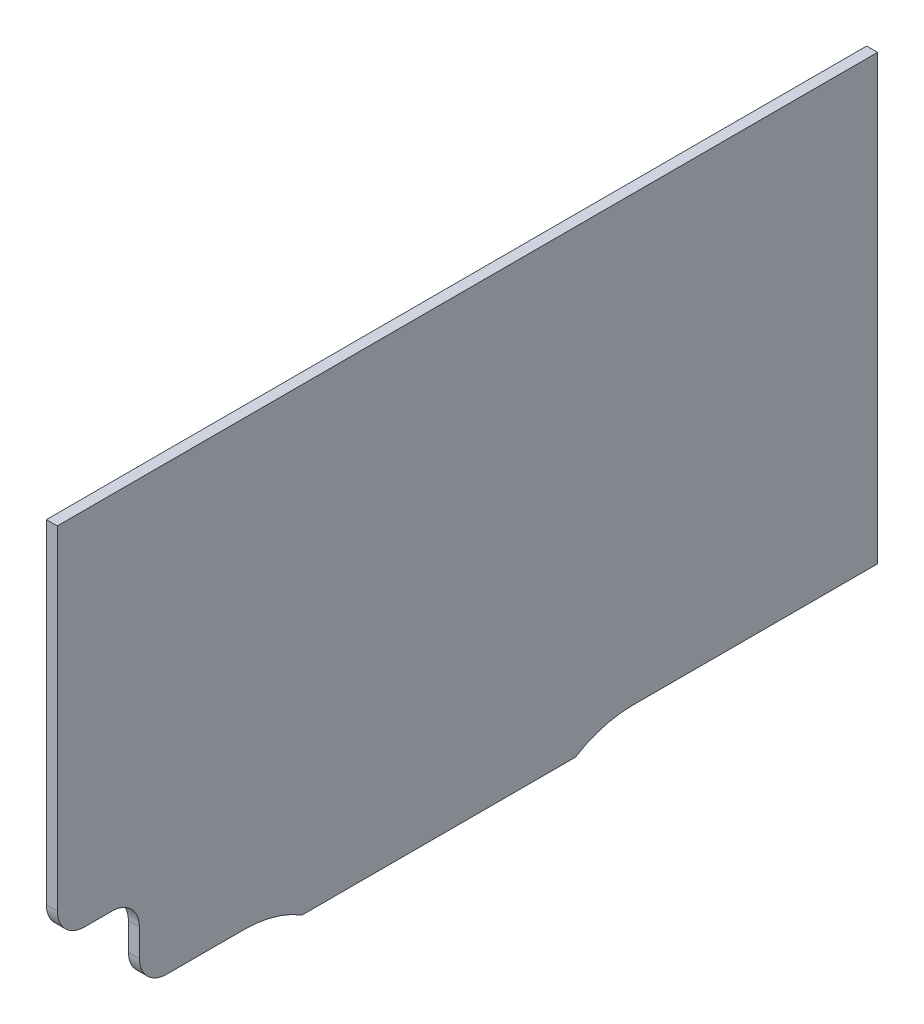
SolidWorks part; units mm, degrees
ref_plane "Alzado" through (0, 0, 0) normal (0, 0, 1) x (1, 0, 0)
ref_plane "Planta" through (0, 0, 0) normal (0, 1, 0) x (1, 0, 0)
ref_plane "Vista lateral" through (0, 0, 0) normal (1, 0, 0) x (0, 0, -1)
sketch "Croquis1" plane through (0, 0, 0) normal (0, 1, 0) x (1, 0, 0)
  line L0 (10, 50) -> (10, 0) construction
  line L1 (0, 0) -> (25, 0)
  line L2 (0, 0) -> (0, 50)
  line L3 (0, 50) -> (25, 50)
  line L4 (25, 0) -> (25, 50)
  circle A0 centre (10, 37.5) radius 1.65
  circle A1 centre (10, 12.5) radius 1.65
  dimension "D3" = 3.3
  dimension "D1" = 50
  dimension "D2" = 25
  dimension "D4" = 25
  dimension "D5" = 12.5
  dimension "D6" = 15
extrude "Saliente-Extruir1" add sketch "Croquis1" along normal blind 3
sketch "Croquis2" plane through (0, 3, 0) normal (0, 1, 0) x (1, 0, 0)
  line L0 (25, 25) -> (18, 25) construction
  line L1 (16, 105.25) -> (18, 105.25)
  line L2 (16, 105.25) -> (16, -44.75)
  line L3 (16, -44.75) -> (18, -44.75)
  line L4 (18, 105.25) -> (18, -44.75)
  line L5 (25, 0) -> (25, 50) construction
  circle A0 centre (10, 37.5) radius 1.65 construction
  dimension "D1" = 2
  dimension "D2" = 6
  dimension "D3" = 150
  dimension "D4" = 80.25
extrude "Saliente-Extruir2" add sketch "Croquis2" along normal blind 81
fillet "Redondeo1" radius 10 2 edges at (0, 1.5, -50) (0, 1.5, 0)
sketch "Croquis3" plane through (0, 3, 0) normal (0, 1, 0) x (1, 0, 0)
  line L1 (25, 50) -> (18, 50)
  line L2 (25, 50) -> (25, 0)
  line L3 (25, 0) -> (18, 0)
  line L4 (18, 50) -> (18, 0)
extrude "Cortar-Extruir1" cut sketch "Croquis3" against normal up to surface (3 mm away) up to face at (10, 0, -35.85)
fillet "Redondeo3" radius 20 2 edges at (17, 3, -50) (17, 3, 0)
fillet "Redondeo4" radius 30 1 edges at (16, 3, -25)
sketch "Croquis4" plane through (16, 0, 0) normal (-1, 0, 0) x (0, 0, 1)
  line L1 (44.75, 3) -> (29.75, 3)
  line L2 (44.75, 3) -> (44.75, 18)
  line L3 (44.75, 18) -> (29.75, 18)
  line L4 (29.75, 3) -> (29.75, 18)
  dimension "D1" = 15
  dimension "D2" = 15
extrude "Cortar-Extruir2" cut sketch "Croquis4" against normal up to surface (2 mm away) up to face at (18, 22.6838, -27.625)
fillet "Redondeo5" radius 5 3 edges at (17, 3, 29.75) (17, 18, 29.75) (17, 18, 44.75)
sketch "Croquis5" plane through (0, 84, 0) normal (0, 1, 0) x (1, 0, 0)
  circle A0 centre (10, 37.5) radius 2.95
  circle A1 centre (10, 12.5) radius 2.95
  dimension "D1" = 5.9
  dimension "D2" = 5.9
extrude "Cortar-Extruir3" cut sketch "Croquis5" against normal blind 80
